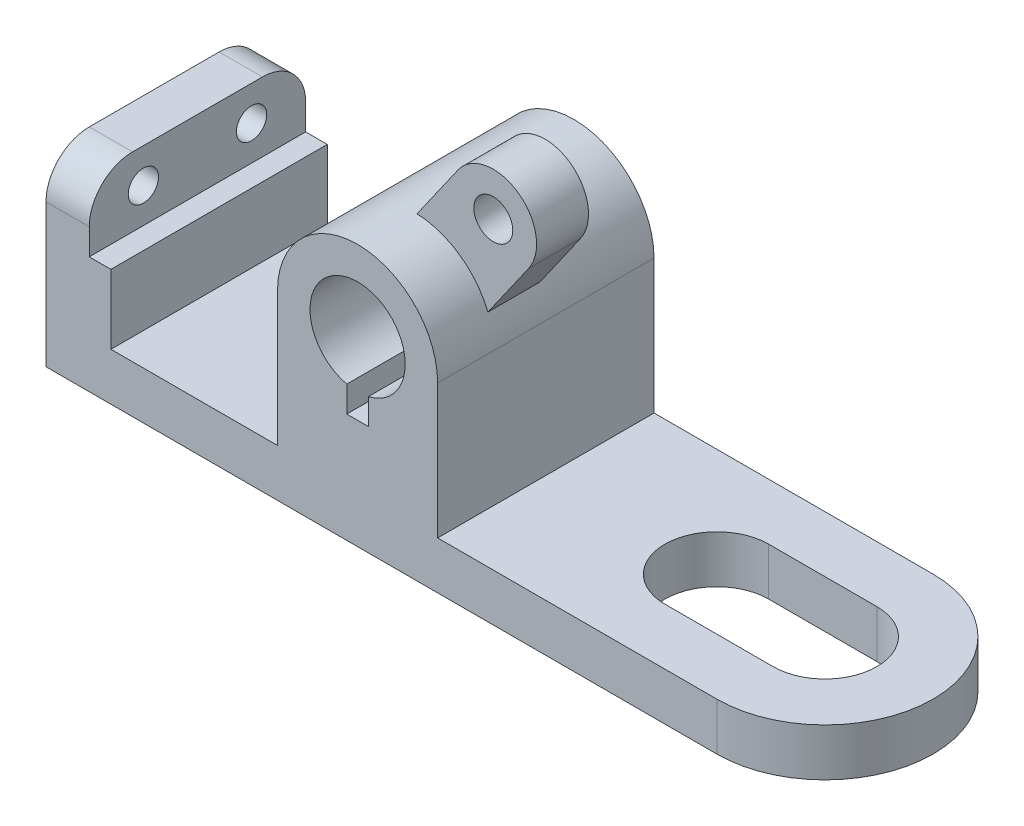
SolidWorks part; units mm, degrees
ref_plane "Front Plane" through (0, 0, 0) normal (0, 0, 1) x (1, 0, 0)
ref_plane "Top Plane" through (0, 0, 0) normal (0, 1, 0) x (1, 0, 0)
ref_plane "Right Plane" through (0, 0, 0) normal (1, 0, 0) x (0, 0, -1)
sketch "Sketch1" plane through (0, 0, 0) normal (0, 0, 1) x (1, 0, 0)
  line L0 (0, 0) -> (0, 43)
  line L1 (0, 43) -> (10, 43)
  line L2 (10, 43) -> (10, 27)
  line L3 (10, 27) -> (15, 27)
  line L4 (15, 27) -> (15, 11)
  line L5 (15, 11) -> (53.5, 11)
  line L6 (0, 0) -> (155, 0)
  line L7 (53.5, 11) -> (53.5, 42)
  line L8 (90.5, 42) -> (90.5, 11)
  line L9 (90.5, 11) -> (155, 11)
  line L10 (155, 11) -> (155, 0)
  line L11 (72.7358, 60.4854) -> (82.1629, 73.9486)
  line L12 (89.1189, 49.0138) -> (98.546, 62.4771)
  line L13 (69.5, 31.2879) -> (69.5, 25.2879)
  line L14 (69.5, 25.2879) -> (74.5, 25.2879)
  line L15 (74.5, 25.2879) -> (74.5, 31.2879)
  line L16 (72, 42) -> (37.7094, 42) construction
  line L17 (72, 42) -> (90.3544, 68.2129) construction
  arc A0 (53.5, 42) -> (90.5, 42) centre (72, 42) cw
  arc A1 (82.1629, 73.9486) -> (98.546, 62.4771) centre (90.3544, 68.2129) cw
  arc A3 (74.5, 31.2879) -> (69.5, 31.2879) centre (72, 42) ccw
  circle A4 centre (90.3544, 68.2129) radius 4.5
  point P27 (0, 0)
  point P29 (0, 0)
  point P30 (0, 0)
  dimension "D4" = 18.5
  dimension "D5" = 11
  dimension "D6" = 5
  dimension "D14" = 10
  dimension "D15" = 9
  dimension "D1" = 16
  dimension "D2" = 43
  dimension "D3" = 72
  dimension "D7" = 6
  dimension "D8" = 11
  dimension "D9" = 42
  dimension "D10" = 5
  dimension "D11" = 15
  dimension "D12" = 32
  dimension "D13" = 55
  dimension "D16" = 155
  dimension "D17" = 11
extrude "Boss-Extrude5" add sketch "Sketch1" along normal blind 25 and the other way blind 25 contours A0 L7 L5 L4 L3 L2 L1 L0 L6 L10 L9 L8 A3 L15 L14 L13 region at (67.0236, 17.7342, 0)
extrude "Boss-Extrude6" add sketch "Sketch1<6>" along normal blind 12 contours A1 L11 A0 L12 A4 region at (82.8417, 57.4835, 0)
sketch "Sketch1<6>" plane through (0, 0, 0) normal (0, 0, 1) x (1, 0, 0) same geometry as "Sketch1"
sketch "Sketch4" plane through (0, 11, 0) normal (0, 1, 0) x (1, 0, 0)
  line L0 (155, 25) -> (155, -25)
  arc A0 (155, 25) -> (155, -25) centre (155, 0) cw
  dimension "D1" = 25
extrude "Boss-Extrude7" add sketch "Sketch4" against normal blind 11
sketch "Sketch5" plane through (10, 0, 0) normal (1, 0, 0) x (0, 0, -1)
  line L0 (-25, 27) -> (-25, 33)
  line L1 (-15, 43) -> (15, 43)
  line L2 (25, 33) -> (25, 27)
  line L3 (-25, 27) -> (-25, 43)
  line L4 (-25, 43) -> (25, 43)
  line L5 (25, 43) -> (25, 27)
  arc A0 (-15, 43) -> (-25, 33) centre (-15, 33) ccw
  arc A1 (15, 43) -> (25, 33) centre (15, 33) cw
  point P10 (-25, 43)
  point P13 (25, 43)
  line M1 (25, 43) -> (-25, 43)
  line M2 (-25, 43) -> (-25, 27)
  line M4 (25, 27) -> (25, 43)
  dimension "D1" = 10
  dimension "D2" = 10
extrude "Cut-Extrude1" cut sketch "Sketch5" against normal blind 11 contours A0 M1 M2 | A1 M1 M4 region at (10, 40.7663, -22.7663) region at (10, 40.7663, 22.7663)
sketch "Sketch6" plane through (10, 0, 0) normal (1, 0, 0) x (0, 0, -1)
  line L0 (0, 34.3509) -> (0, 51.2619) construction
  line L3 (15, 43) -> (-15, 43) construction
  circle A0 centre (-12.5, 35) radius 3.5
  circle A1 centre (12.5, 35) radius 3.5
  dimension "D1" = 7
  dimension "D2" = 8
  dimension "D3" = 12.5
extrude "Cut-Extrude2" cut sketch "Sketch6" against normal blind 11 contours A0 | A1 region at (10, 35, 12.5) region at (10, 35, -12.5)
sketch "Sketch7" plane through (0, 11, 0) normal (0, 1, 0) x (1, 0, 0)
  line L0 (155, 0) -> (130, 0) construction
  line L1 (155, -12) -> (130, -12)
  line L2 (155, 12) -> (130, 12)
  line L3 (90.5, 25) -> (155, 25) construction
  line L4 (0, 15) -> (0, -15) construction
  arc A0 (155, -12) -> (155, 12) centre (155, 0) ccw
  arc A1 (130, 12) -> (130, -12) centre (130, 0) ccw
  point P3 (142.5, 0)
  dimension "D1" = 13
  dimension "D2" = 25
  dimension "D3" = 155
extrude "Cut-Extrude3" cut sketch "Sketch7" against normal blind 11 contours L2 A1 L1 A0 region at (142.5, 11, 0)
